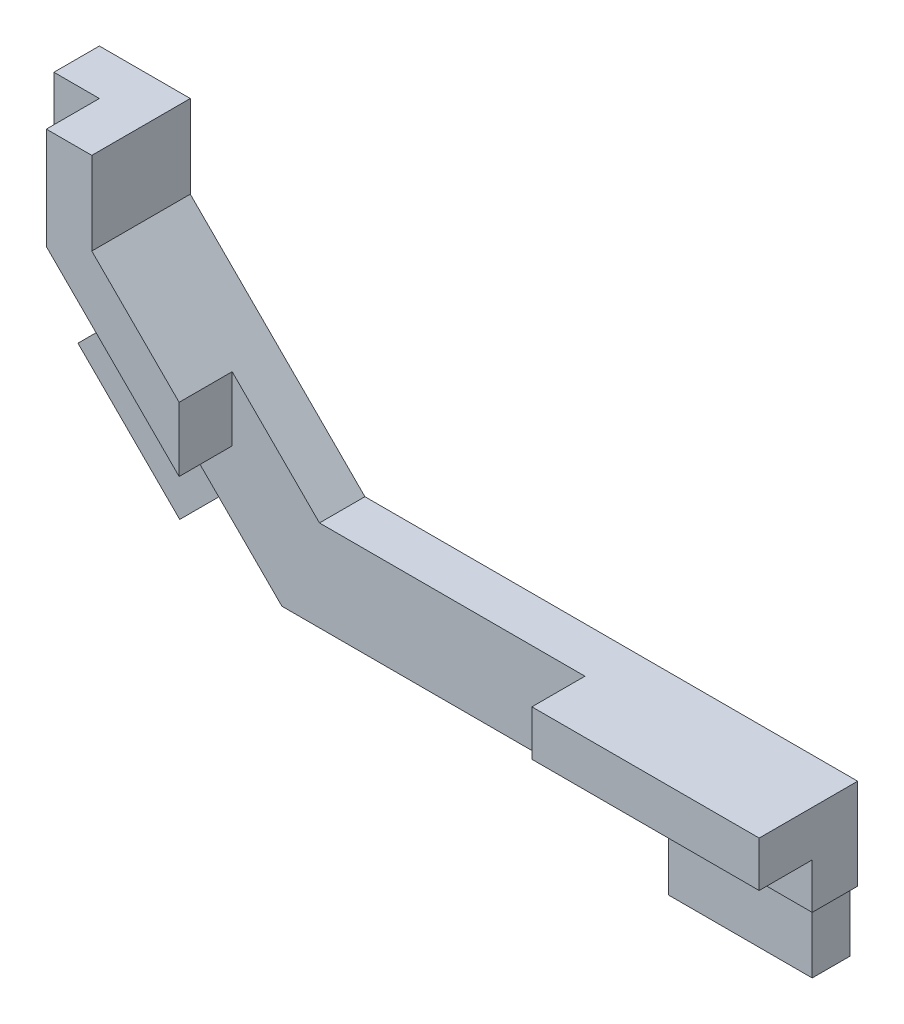
SolidWorks part; units mm, degrees
ref_plane "Front Plane" through (0, 0, 0) normal (0, 0, 1) x (1, 0, 0)
ref_plane "Top Plane" through (0, 0, 0) normal (0, 1, 0) x (1, 0, 0)
ref_plane "Right Plane" through (0, 0, 0) normal (1, 0, 0) x (0, 0, -1)
sketch "Sketch1" plane through (0, 0, 0) normal (0, 1, 0) x (1, 0, 0)
  line L1 (17.5, -1.5) -> (-17.5, -1.5)
  line L2 (17.5, -1.5) -> (17.5, 1.5)
  line L3 (17.5, 1.5) -> (-17.5, 1.5)
  line L4 (-17.5, -1.5) -> (-17.5, 1.5)
  line L5 (17.5, -1.5) -> (-17.5, 1.5) construction
  line L6 (17.5, 1.5) -> (-17.5, -1.5) construction
  point P0 (0, 0)
  dimension "D1" = 3
  dimension "D2" = 35
extrude "Boss-Extrude1" add sketch "Sketch1" along normal blind 6
sketch "Sketch2" plane through (0, 0, 1.5) normal (0, 0, 1) x (1, 0, 0)
  line L0 (-17.5, 0) -> (-32.5472, 15.0472)
  line L1 (-32.5472, 15.0472) -> (-32.5472, 22.9972)
  line L2 (-32.5472, 22.9972) -> (-26.5472, 22.9972)
  line L3 (-26.5472, 22.9972) -> (-26.5472, 17.5272)
  line L4 (-26.5472, 17.5272) -> (-15.02, 6)
  line L5 (-17.5, 6) -> (17.5, 6) construction
  line L6 (-17.5, 0) -> (17.5, 0) construction
  line L7 (-17.5, 0) -> (-17.5, 6)
  line L8 (-17.5, 6) -> (-15.02, 6)
  dimension "D1" = 6
  dimension "D2" = 21.28
  dimension "D3" = 7.95
  dimension "D4" = 135
  dimension "D5" = 5.47
extrude "Boss-Extrude2" add sketch "Sketch2" against normal up to surface (3 mm away) up to face at (0, 3, -1.5)
sketch "Sketch3" plane through (0, 0, 1.5) normal (0, 0, 1) x (1, 0, 0)
  line L0 (-29.5472, 22.9972) -> (-26.5472, 22.9972)
  line L1 (-26.5472, 22.9972) -> (-32.5472, 22.9972) construction
  line L2 (-26.5472, 22.9972) -> (-26.5472, 17.5272)
  line L3 (-26.5472, 17.5272) -> (-20.7836, 11.7636)
  line L4 (2.5, 6) -> (17.5, 6)
  line L5 (17.5, 6) -> (17.5, 3)
  line L6 (17.5, 6) -> (17.5, 0) construction
  line L7 (17.5, 3) -> (2.5, 3)
  line L8 (-20.7836, 7.521) -> (-29.5472, 16.2846)
  line L9 (-29.5472, 16.2846) -> (-29.5472, 22.9972)
  line L10 (2.5, 6) -> (2.5, 3)
  line L11 (-20.7836, 11.7636) -> (-20.7836, 7.521)
  line M11 (17.5, 0) -> (17.5, 6)
  line M12 (17.5, 6) -> (-15.02, 6)
  line M13 (-15.02, 6) -> (-26.5472, 17.5272)
  line M14 (-26.5472, 17.5272) -> (-26.5472, 22.9972)
  line M15 (-26.5472, 22.9972) -> (-32.5472, 22.9972)
  dimension "D1" = 3
  dimension "D2" = 15
  dimension "D3" = 5.7636
  dimension "D4" = 4.2426
extrude "Boss-Extrude3" add sketch "Sketch3" along normal blind 3.5 and the other way up to surface (3 mm away) contours L11 L9 L8 M13 M14 M15 | L10 L7 M12 M11 | L8 L9 L0 L2 L3 L11 | L5 L7 L10 L4 region at (10, 4.5, 1.5) region at (-25.8188, 15.6966, 1.5) other way up to face at (-14.4636, 11.3211, -1.5)
sketch "Sketch4" plane through (0, 0, 0) normal (0, -1, 0) x (1, 0, 0)
  line L0 (17.5, 1.5) -> (17.5, -1.5) construction
  line L1 (7.75, -1.25) -> (17.25, -1.25)
  line L2 (7.75, -1.25) -> (7.75, 1.25)
  line L3 (7.75, 1.25) -> (17.25, 1.25)
  line L4 (17.25, -1.25) -> (17.25, 1.25)
  line L5 (7.75, -1.25) -> (17.25, 1.25) construction
  line L6 (7.75, 1.25) -> (17.25, -1.25) construction
  line L9 (-17.5, 1.5) -> (17.5, 1.5) construction
  line L10 (17.5, -1.5) -> (-17.5, -1.5) construction
  point P0 (12.5, 0)
  dimension "D1" = 9.5
  dimension "D2" = 0.25
  dimension "D3" = 0.25
  dimension "D4" = 0.25
extrude "Boss-Extrude4" add sketch "Sketch4" along normal blind 4
sketch "Sketch5" plane through (-8.75, -8.75, 0) normal (-0.7071, -0.7071, 0) x (0, 0, 1)
  line L0 (-1.5, 23.0144) -> (1.5, 23.0144) construction
  line L1 (-1.5, 12.3744) -> (-1.5, 33.6544) construction
  line L2 (1.5, 33.6544) -> (1.5, 12.3744) construction
  line L4 (1.25, 18.2644) -> (-1.25, 18.2644)
  line L5 (1.25, 18.2644) -> (1.25, 27.7644)
  line L6 (1.25, 27.7644) -> (-1.25, 27.7644)
  line L7 (-1.25, 18.2644) -> (-1.25, 27.7644)
  line L8 (1.25, 18.2644) -> (-1.25, 27.7644) construction
  line L9 (1.25, 27.7644) -> (-1.25, 18.2644) construction
  point P6 (0, 23.0144)
  dimension "D1" = 9.5
  dimension "D2" = 2.5
extrude "Boss-Extrude5" add sketch "Sketch5" along normal blind 4
